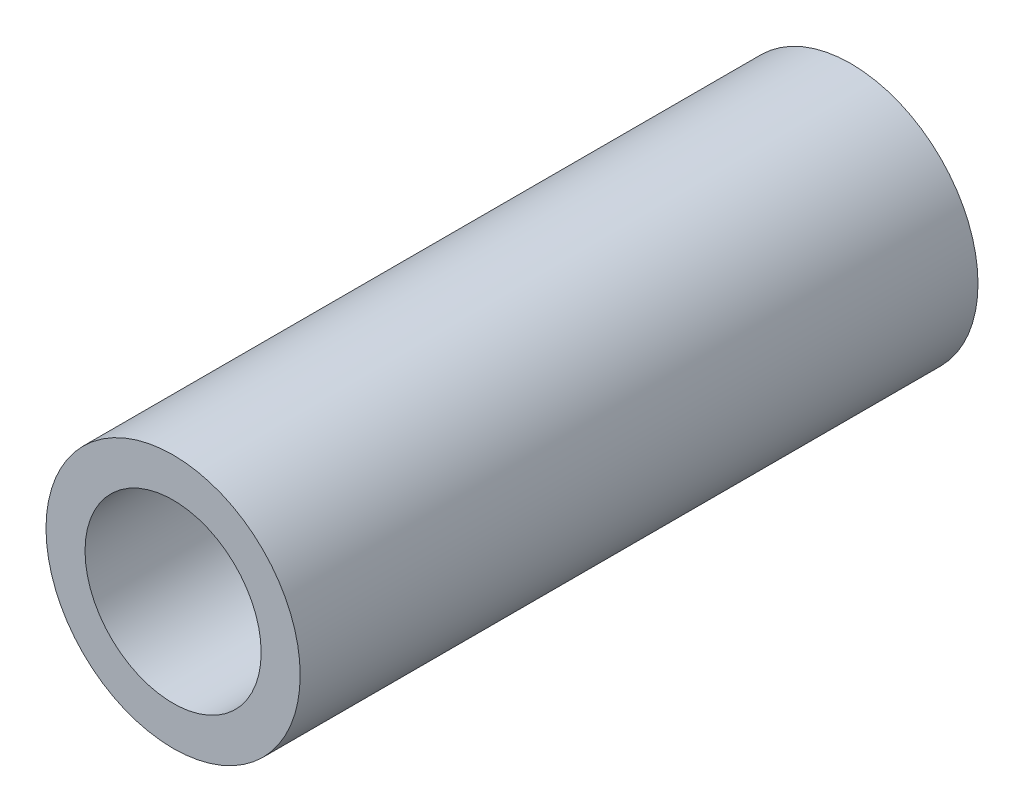
SolidWorks part; units mm, degrees
material "FR-4"
ref_plane "Front Plane" through (0, 0, 0) normal (0, 0, 1) x (1, 0, 0)
ref_plane "Top Plane" through (0, 0, 0) normal (0, 1, 0) x (1, 0, 0)
ref_plane "Right Plane" through (0, 0, 0) normal (1, 0, 0) x (0, 0, -1)
ref_axis "Centre Axis" through (0, 0, -95.34) along (0, 0, 1)
sketch "Sketch1" plane through (0, 0, 0) normal (0, 0, 1) x (1, 0, 0)
  circle A0 centre (0, 0) radius 2.3813
  point P3 (0, 0)
  point P4 (0, 0)
  point P5 (-0.9543, 1.6088)
  dimension "D1" = 4.7625
extrude "Boss-Extrude1" add sketch "Sketch1" against normal blind 12.7
hole_wizard "M4x0.7 Tapped Hole1" positions "Sketch5" profile "Sketch6" tap size "M4x0.7" standard "ANSI Metric" end condition through all
sketch "Sketch5" plane through (0, 0, 0) normal (0, 0, 1) x (1, 0, 0)
  point P0 (0, 0)
  point P3 (0, 0)
  point P4 (-0.7018, -2.7817)
sketch "Sketch6" plane through (0, 0, 0) normal (1, 0, 0) x (0, -1, 0)
  line L0 (0, 0) -> (0, 12.7)
  line L1 (0, 12.7) -> (1.65, 12.7)
  line L2 (1.65, 12.7) -> (1.65, 0)
  line L5 (1.65, 0) -> (0, 0)
  line L11 (0, -6.35) -> (0, 107.95) construction
  dimension "Thru Tap Drill Dia." = 3.3
  dimension "Thru Tap Drill Depth" = 12.7
cosmetic thread "Hole Thread1" parameters "D2"=4
